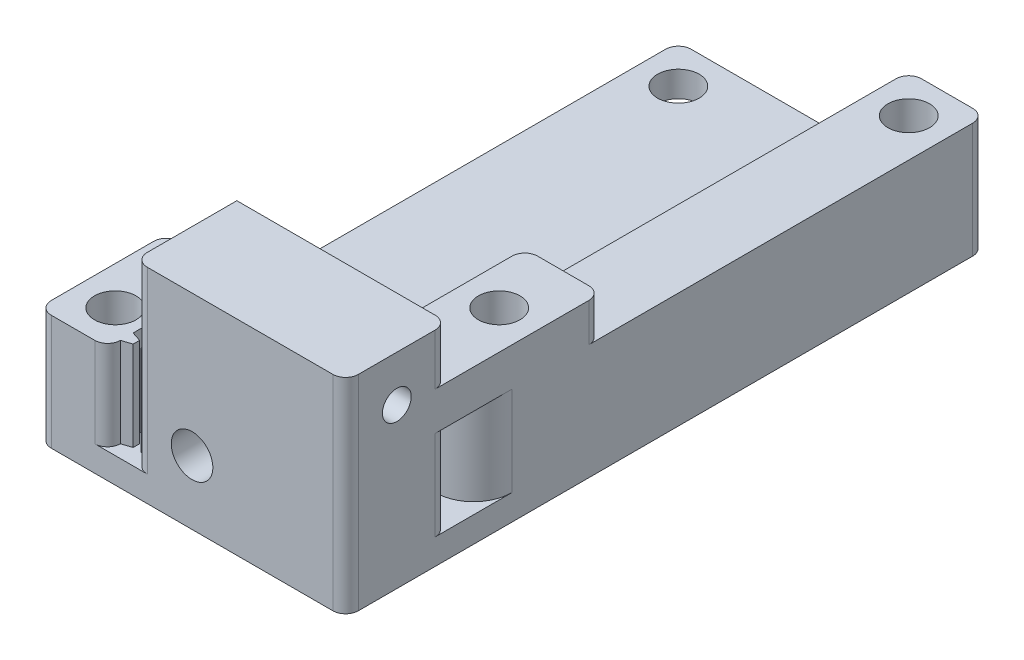
SolidWorks part; units mm, degrees
ref_plane "Front Plane" through (0, 0, 0) normal (0, 0, 1) x (1, 0, 0)
ref_plane "Top Plane" through (0, 0, 0) normal (0, 1, 0) x (1, 0, 0)
ref_plane "Right Plane" through (0, 0, 0) normal (1, 0, 0) x (0, 0, -1)
sketch "Sketch1" plane through (0, 0, 0) normal (0, 1, 0) x (1, 0, 0)
  line L0 (-12, 25) -> (12, -25) construction
  line L1 (-12, 25) -> (12, 25)
  line L2 (-12, 25) -> (-12, -25)
  line L3 (-12, -25) -> (12, -25)
  line L4 (12, 25) -> (12, -25)
  dimension "D1" = 24
  dimension "D2" = 50
extrude "Boss-Extrude1" add sketch "Sketch1" along normal blind 2
sketch "Sketch2" plane through (0, 2, 0) normal (0, 1, 0) x (1, 0, 0)
  line L0 (-12, -25) -> (12, -25) construction
  line L1 (12, 25) -> (6, 25)
  line L2 (12, 25) -> (12, -15)
  line L3 (12, -15) -> (6, -15)
  line L4 (6, 25) -> (6, -15)
  line L5 (-12, 25) -> (-12, -25) construction
  line L6 (-4.5, -25) -> (4.5, -25)
  line L7 (-4.5, -25) -> (-4.5, -15)
  line L8 (-4.5, -15) -> (4.5, -15)
  line L9 (4.5, -25) -> (4.5, -15)
  line L10 (-12, -15) -> (-6.6, -15)
  line L11 (-12, -15) -> (-12, -25)
  line L12 (-12, -25) -> (-6.6, -25)
  line L13 (-6.6, -15) -> (-6.6, -25)
  dimension "D1" = 6
  dimension "D2" = 10
  dimension "D3" = 10
  dimension "D4" = 2.1
  dimension "D5" = 1.5
  dimension "D6" = 9
extrude "Boss-Extrude2" add sketch "Sketch2" along normal blind 7
fillet "Fillet1" radius 3 2 edges at (12, 5.5, 15) (6, 5.5, 15)
sketch "Sketch3" plane through (0, 2, 0) normal (0, 1, 0) x (1, 0, 0)
  line L0 (-4.5, -15) -> (-4.5, -25) construction
  line L1 (12, -25) -> (-4.5, -25)
  line L2 (12, -25) -> (12, -17)
  line L3 (12, -17) -> (-4.5, -17)
  line L4 (-4.5, -25) -> (-4.5, -17)
  line L5 (4.5, -15) -> (-4.5, -15) construction
  dimension "D1" = 2
extrude "Boss-Extrude3" add sketch "Sketch3" along normal blind 14
sketch "Sketch4" plane through (0, 0, 15) normal (0, 0, -1) x (-1, 0, 0)
  line L0 (0, 9) -> (0, 5) construction
  line L1 (-4.5, 9) -> (4.5, 9) construction
  circle A0 centre (0, 5) radius 1.625
  dimension "D1" = 3.25
  dimension "D2" = 4
extrude "Cut-Extrude1" cut sketch "Sketch4" against normal through all
sketch "Sketch5" plane through (0, 0, 15) normal (0, 0, -1) x (-1, 0, 0)
  line L0 (0, 9) -> (0, 5) construction
  line L1 (-4.5, 9) -> (4.5, 9) construction
  line L2 (-2.875, 6.6599) -> (-2.875, 9)
  line L3 (0, 8.3198) -> (-2.875, 6.6599) construction
  line L4 (-2.875, 6.6599) -> (-2.875, 3.3401)
  line L5 (-2.875, 3.3401) -> (0, 1.6802)
  line L6 (0, 1.6802) -> (2.875, 3.3401)
  line L7 (2.875, 3.3401) -> (2.875, 6.6599)
  line L8 (2.875, 6.6599) -> (0, 8.3198) construction
  line L9 (-4.5, 9) -> (4.5, 9) construction
  line L10 (2.875, 6.6599) -> (2.875, 9)
  line L11 (2.875, 9) -> (-2.875, 9)
  circle A0 centre (0, 5) radius 2.875 construction
  dimension "D1" = 5.75
extrude "Cut-Extrude2" cut sketch "Sketch5" against normal blind 2
sketch "Sketch9" plane through (0, 9, 0) normal (0, 1, 0) x (1, 0, 0)
  line L0 (6, 25) -> (6, -12) construction
  line L1 (6, -5) -> (12, -5)
  line L2 (6, -5) -> (6, -25)
  line L3 (6, -25) -> (12, -25)
  line L4 (12, -5) -> (12, -25)
  dimension "D1" = 20
extrude "Boss-Extrude4" add sketch "Sketch9" along normal blind 3
sketch "Sketch6" plane through (12, 0, 0) normal (1, 0, 0) x (0, 0, -1)
  line L0 (-21, 16) -> (-21, 12.43) construction
  line L1 (-25, 16) -> (-17, 16) construction
  line L2 (-25, 0) -> (25, 0) construction
  circle A0 centre (-21, 12.43) radius 1.125
  dimension "D1" = 2.25
  dimension "D2" = 12.43
extrude "Cut-Extrude3" cut sketch "Sketch6" against normal through all
sketch "Sketch7" plane through (0, 2, 0) normal (0, 1, 0) x (1, 0, 0)
  line L0 (0, -15) -> (0, 25) construction
  line L1 (4.5, -15) -> (0.5538, -15) construction
  line L2 (6, 25) -> (-12, 25) construction
  line L4 (-1, 25) -> (1, 25)
  line L5 (-1, 25) -> (-1, -15)
  line L6 (-1, -15) -> (1, -15)
  line L7 (1, 25) -> (1, -15)
  dimension "D1" = 2
extrude "Cut-Extrude4" cut sketch "Sketch7" against normal blind 1
sketch "Sketch8" plane through (0, 0, 0) normal (0, -1, 0) x (1, 0, 0)
  line L5 (-12, 25) -> (12, 25) construction
  line L8 (-9, 22) -> (-9, -22)
  line L9 (-9, -22) -> (9, -22)
  line L10 (9, -22) -> (9, 22)
  line L11 (9, 22) -> (-9, 22)
  line L12 (-9, 22) -> (-9, -22) construction
  line L13 (-9, -22) -> (9, -22) construction
  line L14 (9, -22) -> (9, 22) construction
  line L15 (9, 22) -> (-9, 22) construction
  circle A0 centre (-9, 22) radius 1.625
  circle A1 centre (9, 10) radius 1.625
  circle A2 centre (9, -22) radius 1.625
  circle A3 centre (-9, -22) radius 1.625
  dimension "D2" = 3.25
  dimension "D3" = 15
  dimension "D1" = 3
extrude "Cut-Extrude5" cut sketch "Sketch8" against normal through all
fillet "Fillet2" radius 1 12 edges at (-12, 1, -25) (6, 5.5, -25) (-4.5, 9, 25) (-6.6, 5.5, 25) (-12, 5.5, 15) (-12, 4.5, 25) (12, 8, 25) (12, 4.5, -25) (12, 14, 17) (12, 5.5, 17) (6, 10.5, 5) (12, 10.5, 5)
sketch "Sketch10" plane through (0, 2, 0) normal (0, 1, 0) x (1, 0, 0)
  line L0 (-6.6, -24) -> (-6.6, -23)
  line L1 (-6.6, -24) -> (-6.6, -15) construction
  line L2 (-6.6, -23) -> (-5.85, -23.25)
  line L3 (-5.85, -23.25) -> (-5.85, -23.75)
  line L4 (-5.85, -23.75) -> (-6.6, -24)
  line L5 (-6.6, -24) -> (-4.5, -24) construction
  line L6 (-5.55, -24) -> (-5.55, 25) construction
  line L7 (-1, 25) -> (-11, 25) construction
  line L8 (-6.6, -23.5) -> (-5.85, -23.5) construction
  line L9 (-5.25, -23.75) -> (-4.5, -24)
  line L10 (-5.25, -23.25) -> (-5.25, -23.75)
  line L11 (-4.5, -23) -> (-5.25, -23.25)
  line L12 (-4.5, -24) -> (-4.5, -23)
  dimension "D1" = 0.75
  dimension "D2" = 1
  dimension "D3" = 0.5
extrude "Boss-Extrude5" add sketch "Sketch10" along normal up to surface (7 mm away) up to face at (-9, 9, 23.625)
pattern_linear "LPattern1" count 5 spacing 2 along (0, 0, -1) of "Boss-Extrude5"
